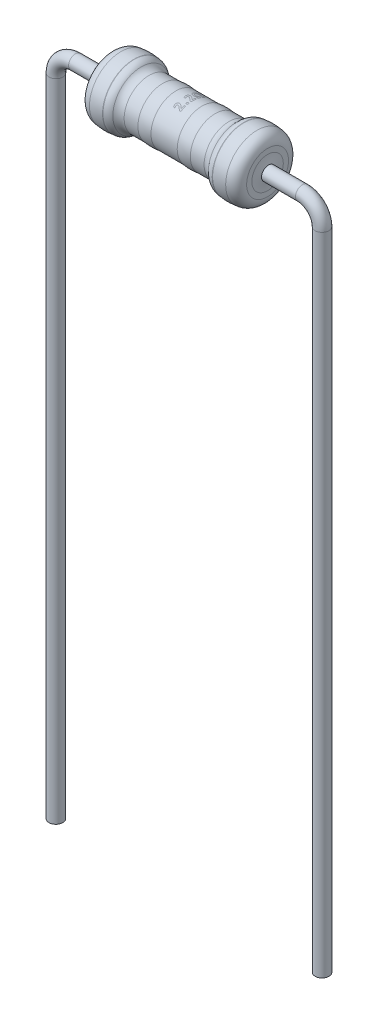
SolidWorks part; units mm, degrees
material "Plain Carbon Steel"
ref_plane "Front Plane" through (0, 0, 0) normal (0, 0, 1) x (1, 0, 0)
ref_plane "Top Plane" through (0, 0, 0) normal (0, 1, 0) x (1, 0, 0)
ref_plane "Right Plane" through (0, 0, 0) normal (1, 0, 0) x (0, 0, -1)
sketch "Sketch1" plane through (0, 0, 0) normal (0, 0, 1) x (1, 0, 0)
  line L0 (-4.33, 0) -> (4.33, 0)
  line L1 (-5.08, -0.75) -> (-5.08, -25.4)
  line L2 (5.08, -0.75) -> (5.08, -25.4)
  line L3 (-5.08, -25.4) -> (5.08, -25.4) construction
  line L4 (0, 0) -> (0, -25.4) construction
  arc A0 (-4.33, 0) -> (-5.08, -0.75) centre (-4.33, -0.75) ccw
  arc A1 (4.33, 0) -> (5.08, -0.75) centre (4.33, -0.75) cw
  dimension "D2" = 0.75
  dimension "D1" = 10.16
  dimension "D3" = 25.4
ref_plane "Plane1" through (-5.08, -25.4, 0) normal (0, -1, 0) x (-1, 0, 0)
sketch "Sketch2" plane through (-5.08, -25.4, 0) normal (0, -1, 0) x (-1, 0, 0)
  circle A0 centre (0, 0) radius 0.265
  dimension "D1" = 0.53
sweep "Sweep1" add profiles "Sketch2" path "Sketch1"
sketch "Sketch3" plane through (0, 0, 0) normal (0, 0, 1) x (1, 0, 0)
  line L0 (-3, 0) -> (3, 0)
  line L5 (-3, 0) -> (-3, 1.2)
  line L6 (3, 0) -> (3, 1.2)
  line L7 (-3, 1.2) -> (-1.75, 1.2)
  line L8 (3, 1.2) -> (1.75, 1.2)
  line L9 (-1.75, 1.2) -> (-1.75, 0.95)
  line L10 (-1.75, 0.95) -> (1.75, 0.95)
  line L11 (1.75, 0.95) -> (1.75, 1.2)
  line L12 (0, 0) -> (0, 0.95) construction
  dimension "D1" = 6
  dimension "D2" = 1.2
  dimension "D3" = 3.5
  dimension "D4" = 0.95
  dimension "D5" = 0.25
revolve "Revolve1" add sketch "Sketch3" angle 360 about L0
fillet "Fillet-1" radius 0.35 2 edges at (1.75, 0, 1.2) (-1.75, 0, 1.2)
fillet "Fillet-2" radius 0.4 4 edges at (3, 0, 1.2) (-3, 0, 1.2) (1.75, 0, 0.95) (-1.75, 0, 0.95)
sketch "Sketch5" plane through (0, 0, 0) normal (0, 0, 1) x (1, 0, 0)
  line L16 (-3, 0) -> (3, 0) construction
  line L17 (-2.6, 1.2) -> (-2.1, 1.2) construction
  line L18 (-2.6, 1.2) -> (-2.6, 0)
  line L19 (-2.6, 0) -> (-2.1, 0)
  line L20 (-2.1, 1.2) -> (-2.1, 0)
  line L21 (-1.75, 0.95) -> (1.75, 0.95) construction
  line L22 (2.6, 1.2) -> (2.1, 1.2) construction
  line L23 (2.6, 1.2) -> (2.6, 0)
  line L24 (2.6, 0) -> (2.1, 0)
  line L25 (2.1, 1.2) -> (2.1, 0)
  line L26 (-0.5, 0.95) -> (-1, 0.95) construction
  line L27 (-0.5, 0.95) -> (-0.5, 0)
  line L28 (-0.5, 0) -> (-1, 0)
  line L29 (-1, 0.95) -> (-1, 0)
  line L30 (-2.35, 1.2) -> (-2.35, 1.22) construction
  line L31 (1, 0.95) -> (0.5, 0.95) construction
  line L32 (1, 0.95) -> (1, 0)
  line L33 (1, 0) -> (0.5, 0)
  line L34 (0.5, 0.95) -> (0.5, 0)
  line L35 (-0.75, 0.95) -> (-0.75, 0.97) construction
  line L36 (0.75, 0.95) -> (0.75, 0.97) construction
  line L37 (2.35, 1.2) -> (2.35, 1.22) construction
  line L48 (-3, 0) -> (-3, 0.6)
  line L49 (-3, 0) -> (-3, 1.2) construction
  line L50 (-3, 0) -> (-3.05, 0)
  line L51 (-3.05, 0) -> (-3.05, 0.2)
  line L52 (3, 0) -> (3.05, 0)
  line L53 (3.05, 0) -> (3.05, 0.2)
  line L54 (3, 0) -> (3, 0.6)
  line L55 (3, 0) -> (3, 1.2) construction
  arc A0 (-2.6, 1.2) -> (-2.1, 1.2) centre (-2.35, -0.3525) cw
  arc A1 (-1, 0.95) -> (-0.5, 0.95) centre (-0.75, -0.6025) cw
  arc A2 (0.5, 0.95) -> (1, 0.95) centre (0.75, -0.6025) cw
  arc A3 (2.1, 1.2) -> (2.6, 1.2) centre (2.35, -0.3525) cw
  arc A6 (-3, 0.6) -> (-3.05, 0.2) centre (-4.625, 0.6) cw
  arc A7 (3.05, 0.2) -> (3, 0.6) centre (4.625, 0.6) cw
  dimension "D4" = 0.02
  dimension "D5" = 0.05
  dimension "D7" = 0.6
  dimension "D1" = 0.5
  dimension "D2" = 0.5
  dimension "D3" = 0.5
  dimension "D6" = 0.2
revolve "Revolve3" add sketch "Sketch5" angle 360 about L19
ref_plane "Plane2" through (0, 2, 0) normal (0, 1, 0) x (1, 0, 0)
sketch "Sketch6" plane through (0, 2, 0) normal (0, 1, 0) x (1, 0, 0)
  line L0 (0, 0) -> (0.15, 0) construction
  line L1 (0.15, 0.95) -> (0.15, -0.95) construction
  line L2 (0.5, 0.95) -> (-0.5, 0.95) construction
  text T0 "2.2Ω" font "Calibri" height 0.3
  dimension "D1" = 0.15
wrap "Wrap1" sketch "Sketch6" wrap type scribe source sketch "Sketch6" face at (-0.5, -0.95, 0)
